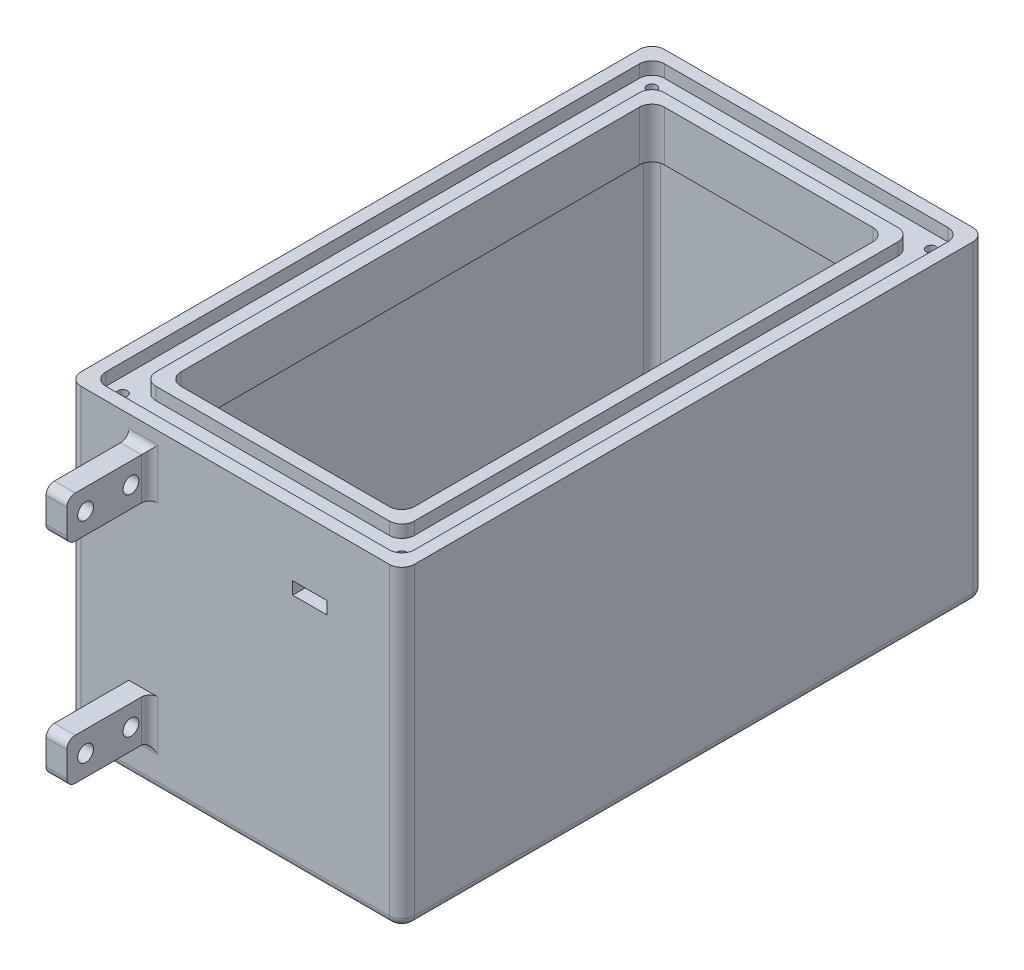
SolidWorks part; units mm, degrees
material "ABS"
ref_plane "Front Plane" through (0, 0, 0) normal (0, 0, 1) x (1, 0, 0)
ref_plane "Top Plane" through (0, 0, 0) normal (0, 1, 0) x (1, 0, 0)
ref_plane "Right Plane" through (0, 0, 0) normal (1, 0, 0) x (0, 0, -1)
sketch "Sketch1" plane through (0, 0, 0) normal (0, 1, 0) x (1, 0, 0)
  line L1 (0, 0) -> (80, 0)
  line L2 (0, 0) -> (0, 140)
  line L3 (0, 140) -> (80, 140)
  line L4 (80, 0) -> (80, 140)
  dimension "D1" = 140
  dimension "D2" = 80
extrude "Boss-Extrude1" add sketch "Sketch1" along normal blind 3
sketch "Sketch2" plane through (0, 3, 0) normal (0, 1, 0) x (1, 0, 0)
  line L1 (0, 140) -> (80, 140)
  line L2 (0, 140) -> (0, 0)
  line L3 (0, 0) -> (80, 0)
  line L4 (80, 140) -> (80, 0)
  line L5 (3, 137) -> (77, 137)
  line L6 (3, 137) -> (3, 3)
  line L7 (3, 3) -> (77, 3)
  line L8 (77, 137) -> (77, 3)
  dimension "D1" = 3
  dimension "D2" = 3
  dimension "D3" = 3
  dimension "D4" = 3
extrude "Boss-Extrude2" add sketch "Sketch2" along normal blind 60
fillet "Fillet1" radius 2 8 edges at (40, 3, -3) (77, 3, -70) (3, 3, -70) (40, 3, -137) (77, 33, -3) (3, 33, -3) (77, 33, -137) (3, 33, -137)
fillet "Fillet2" radius 2 4 edges at (40, 0, -140) (0, 0, -70) (40, 0, 0) (80, 0, -70)
sketch "Sketch6" plane through (0, 63, 0) normal (0, 1, 0) x (1, 0, 0)
  line L1 (0, 140) -> (80, 140)
  line L2 (0, 140) -> (0, 0)
  line L3 (0, 0) -> (80, 0)
  line L4 (80, 140) -> (80, 0)
  line L5 (15, 128) -> (65, 128)
  line L6 (12, 125) -> (12, 15)
  line L7 (15, 12) -> (65, 12)
  line L8 (68, 125) -> (68, 15)
  arc A0 (65, 12) -> (68, 15) centre (65, 15) ccw
  arc A1 (12, 15) -> (15, 12) centre (15, 15) ccw
  arc A2 (65, 128) -> (68, 125) centre (65, 125) cw
  arc A3 (15, 128) -> (12, 125) centre (15, 125) ccw
  dimension "D5" = 3
  dimension "D1" = 12
  dimension "D2" = 12
  dimension "D3" = 12
  dimension "D4" = 12
extrude "Boss-Extrude3" add sketch "Sketch6" along normal blind 12
sketch "Sketch7" plane through (0, 75, 0) normal (0, 1, 0) x (1, 0, 0)
  line L0 (80, 140) -> (0, 140) construction
  line L1 (6, 137) -> (74, 137)
  line L2 (3, 134) -> (3, 6)
  line L3 (6, 3) -> (74, 3)
  line L4 (77, 134) -> (77, 6)
  line L5 (80, 0) -> (80, 140) construction
  line L6 (0, 0) -> (80, 0) construction
  line L7 (0, 140) -> (0, 0) construction
  line L13 (12, 131) -> (68, 131)
  line L14 (9, 128) -> (9, 12)
  line L15 (12, 9) -> (68, 9)
  line L16 (71, 128) -> (71, 12)
  arc A0 (3, 6) -> (6, 3) centre (6, 6) ccw
  arc A1 (74, 3) -> (77, 6) centre (74, 6) ccw
  arc A2 (74, 137) -> (77, 134) centre (74, 134) cw
  arc A3 (6, 137) -> (3, 134) centre (6, 134) ccw
  arc A7 (9, 12) -> (12, 9) centre (12, 12) ccw
  arc A8 (68, 9) -> (71, 12) centre (68, 12) ccw
  arc A9 (68, 131) -> (71, 128) centre (68, 128) cw
  arc A10 (12, 131) -> (9, 128) centre (12, 128) ccw
  dimension "D5" = 3
  dimension "D6" = 6
  dimension "D10" = 3
  dimension "D1" = 3
  dimension "D2" = 3
  dimension "D3" = 3
  dimension "D4" = 3
  dimension "D7" = 6
  dimension "D8" = 6
  dimension "D9" = 6
extrude "Cut-Extrude1" cut sketch "Sketch7" against normal blind 3
sketch "Sketch8" plane through (0, 72, 0) normal (0, 1, 0) x (1, 0, 0)
  line L0 (0, 0) -> (80, 0) construction
  line L1 (0, 140) -> (0, 0) construction
  line L2 (80, 0) -> (80, 140) construction
  line L3 (80, 140) -> (0, 140) construction
  circle A0 centre (6.5, 6.5) radius 1.15
  circle A1 centre (73.5, 6.5) radius 1.15
  circle A2 centre (73.5, 133.5) radius 1.15
  circle A3 centre (6.5, 133.5) radius 1.15
  dimension "D1" = 2.3
  dimension "D2" = 2.3
  dimension "D3" = 2.3
  dimension "D4" = 2.3
  dimension "D5" = 6.5
  dimension "D6" = 6.5
  dimension "D7" = 6.5
  dimension "D8" = 6.5
  dimension "D9" = 6.5
  dimension "D10" = 6.5
  dimension "D11" = 6.5
  dimension "D12" = 6.5
extrude "Cut-Extrude2" cut sketch "Sketch8" against normal blind 6
fillet "Fillet3" radius 3 8 edges at (0.5858, 0.5858, -139.4142) (79.4142, 0.5858, -139.4142) (79.4142, 0.5858, -0.5858) (0.5858, 0.5858, -0.5858) (0, 38.5, -140) (80, 38.5, -140) (80, 38.5, 0) (0, 38.5, 0)
sketch "Sketch9" plane through (0, 0, 0) normal (-1, 0, 0) x (0, 0, 1)
  line L0 (-137, 75) -> (-3, 75) construction
  line L1 (-87, 55) -> (-82, 55)
  line L2 (-87, 55) -> (-87, 25)
  line L3 (-87, 25) -> (-82, 25)
  line L4 (-82, 55) -> (-82, 25)
  line L6 (-140, 2) -> (-140, 75) construction
  line L7 (0, 75) -> (0, 2) construction
  dimension "D1" = 30
  dimension "D2" = 5
  dimension "D3" = 20
  dimension "D4" = 53
  dimension "D5" = 82
extrude "Boss-Extrude4" add sketch "Sketch9" along normal blind 15
sketch "Sketch10" plane through (0, 0, -87) normal (0, 0, -1) x (-1, 0, 0)
  line L0 (15, 25) -> (0, 25) construction
  line L1 (15, 55) -> (10, 55)
  line L2 (15, 55) -> (15, 25)
  line L3 (15, 25) -> (10, 25)
  line L4 (10, 55) -> (10, 25)
  dimension "D1" = 5
extrude "Boss-Extrude5" add sketch "Sketch10" along normal blind 53
fillet "Fillet4" radius 3 4 edges at (0, 25, -84.5) (0, 55, -84.5) (0, 40, -87) (0, 40, -82)
fillet "Fillet5" radius 3 4 edges at (-12.5, 25, -140) (-12.5, 55, -140) (-10, 40, -87) (-15, 40, -82)
sketch "Sketch12" plane through (0, 0, 0) normal (0, 0, 1) x (1, 0, 0)
  line L0 (0, 2) -> (0, 75) construction
  line L1 (14.5, 70) -> (19.5, 70)
  line L2 (14.5, 70) -> (14.5, 60)
  line L3 (14.5, 60) -> (19.5, 60)
  line L4 (19.5, 70) -> (19.5, 60)
  line L5 (14.5, 19.67) -> (19.5, 19.67)
  line L6 (14.5, 19.67) -> (14.5, 9.67)
  line L7 (14.5, 9.67) -> (19.5, 9.67)
  line L8 (19.5, 19.67) -> (19.5, 9.67)
  line L9 (3, 75) -> (77, 75) construction
  dimension "D1" = 5
  dimension "D2" = 10
  dimension "D3" = 5
  dimension "D4" = 10
  dimension "D5" = 40.33
  dimension "D6" = 14.5
  dimension "D7" = 5
extrude "Boss-Extrude6" add sketch "Sketch12" along normal blind 19.88
fillet "Fillet6" radius 2 4 edges at (17, 9.67, 0) (19.5, 14.67, 0) (19.5, 65, 0) (17, 70, 0)
fillet "Fillet7" radius 2 4 edges at (17, 9.67, 19.88) (17, 19.67, 19.88) (17, 60, 19.88) (17, 70, 19.88)
sketch "Sketch13" plane through (14.5, 0, 0) normal (-1, 0, 0) x (0, 0, 1)
  line L0 (0, 65) -> (19.88, 65) construction
  line L2 (19.88, 68) -> (19.88, 62) construction
  line L3 (0, 14.67) -> (19.88, 14.67) construction
  line L5 (19.88, 17.67) -> (19.88, 11.67) construction
  line L6 (0, 19.67) -> (0, 7.67) construction
  line L7 (0, 72) -> (0, 60) construction
  circle A0 centre (4.5, 65) radius 1.9
  circle A1 centre (15.38, 65) radius 1.9
  circle A2 centre (4.5, 14.67) radius 1.9
  circle A3 centre (15.38, 14.67) radius 1.9
  point P8 (0, 65)
  point P9 (0, 0)
  dimension "D1" = 3.8
  dimension "D2" = 3.8
  dimension "D3" = 3.8
  dimension "D4" = 3.8
  dimension "D5" = 4.5
  dimension "D6" = 4.5
  dimension "D7" = 4.5
  dimension "D8" = 4.5
extrude "Cut-Extrude3" cut sketch "Sketch13" against normal through all
sketch "Sketch14" plane through (0, 0, 0) normal (0, 0, 1) x (1, 0, 0)
  line L0 (3, 75) -> (77, 75) construction
  line L1 (53.8, 60) -> (62, 60)
  line L2 (53.8, 60) -> (53.8, 57)
  line L3 (53.8, 57) -> (62, 57)
  line L4 (62, 60) -> (62, 57)
  line L5 (77, 2) -> (77, 75) construction
  dimension "D1" = 8.2
  dimension "D2" = 3
  dimension "D3" = 15
  dimension "D4" = 15
extrude "Cut-Extrude4" cut sketch "Sketch14" against normal blind 3
sketch "Sketch15" plane through (0, 0, 0) normal (0, -1, 0) x (1, 0, 0)
  line L0 (0, -70) -> (80, -70) construction
  line L1 (0, -137) -> (0, -3) construction
  line L2 (80, -3) -> (80, -137) construction
  line L3 (40, 0) -> (40, -140) construction
  line L4 (3, 0) -> (77, 0) construction
  line L5 (77, -140) -> (3, -140) construction
  line L7 (21.25, -44.75) -> (58.75, -44.75)
  line L8 (19.75, -46.25) -> (19.75, -93.75)
  line L9 (21.25, -95.25) -> (58.75, -95.25)
  line L10 (60.25, -46.25) -> (60.25, -93.75)
  line L11 (19.75, -44.75) -> (60.25, -95.25) construction
  line L12 (19.75, -95.25) -> (60.25, -44.75) construction
  line L13 (19.25, -42.75) -> (60.75, -42.75)
  line L14 (17.75, -44.25) -> (17.75, -95.75)
  line L15 (19.25, -97.25) -> (60.75, -97.25)
  line L16 (62.25, -44.25) -> (62.25, -95.75)
  line L17 (17.75, -42.75) -> (62.25, -97.25) construction
  line L18 (17.75, -97.25) -> (62.25, -42.75) construction
  arc A0 (19.75, -93.75) -> (21.25, -95.25) centre (21.25, -93.75) ccw
  arc A1 (17.75, -95.75) -> (19.25, -97.25) centre (19.25, -95.75) ccw
  arc A2 (58.75, -95.25) -> (60.25, -93.75) centre (58.75, -93.75) ccw
  arc A3 (60.75, -97.25) -> (62.25, -95.75) centre (60.75, -95.75) ccw
  arc A4 (58.75, -44.75) -> (60.25, -46.25) centre (58.75, -46.25) cw
  arc A5 (60.75, -42.75) -> (62.25, -44.25) centre (60.75, -44.25) cw
  arc A6 (21.25, -44.75) -> (19.75, -46.25) centre (21.25, -46.25) ccw
  arc A7 (19.25, -42.75) -> (17.75, -44.25) centre (19.25, -44.25) ccw
  point P12 (40, -70)
  point P17 (40, -70)
  dimension "D5" = 1.5
  dimension "D1" = 40.5
  dimension "D2" = 50.5
  dimension "D3" = 2
  dimension "D4" = 2
extrude "Boss-Extrude7" add sketch "Sketch15" along normal blind 1.35
sketch "Sketch16" plane through (0, 0, 0) normal (0, -1, 0) x (1, 0, 0)
  line L0 (40, -44.75) -> (40, -95.25) construction
  line L1 (58.75, -44.75) -> (21.25, -44.75) construction
  line L2 (21.25, -95.25) -> (58.75, -95.25) construction
  line L4 (37.5, -46.68) -> (42.5, -46.68)
  line L5 (37.5, -46.68) -> (37.5, -49.38)
  line L6 (37.5, -49.38) -> (42.5, -49.38)
  line L7 (42.5, -46.68) -> (42.5, -49.38)
  line L8 (37.5, -46.68) -> (42.5, -49.38) construction
  line L9 (37.5, -49.38) -> (42.5, -46.68) construction
  point P6 (40, -48.03)
  dimension "D1" = 5
  dimension "D2" = 2.7
  dimension "D3" = 1.93
extrude "Cut-Extrude5" cut sketch "Sketch16" against normal blind 3
